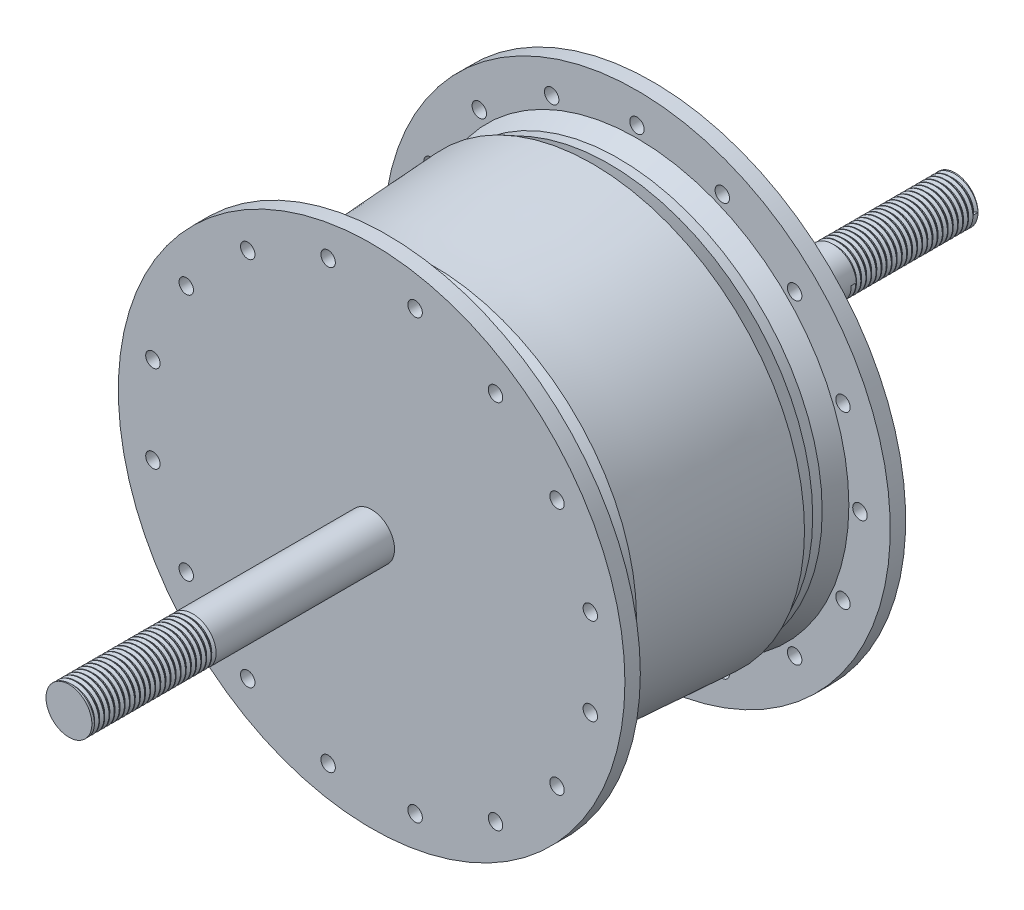
SolidWorks part; units mm, degrees
ref_plane "Front Plane" through (0, 0, 0) normal (0, 0, 1) x (1, 0, 0)
ref_plane "Top Plane" through (0, 0, 0) normal (0, 1, 0) x (1, 0, 0)
ref_plane "Right Plane" through (0, 0, 0) normal (1, 0, 0) x (0, 0, -1)
sketch "Sketch1" plane through (0, 0, 0) normal (1, 0, 0) x (0, 0, -1)
  line L0 (-25.95, 44) -> (-21.711, 41.0448)
  line L1 (-21.711, 41.0448) -> (-20.0488, 41.0448)
  line L2 (-20.0488, 41.0448) -> (-16.448, 42.2998)
  line L3 (-16.448, 42.2998) -> (-8.6389, 42.2998) construction
  line L4 (-8.6389, 42.2998) -> (0, 43.18) construction
  line L5 (0, 43.18) -> (16.7404, 44) construction
  line L6 (16.7404, 44) -> (20.1458, 42.2998)
  line L7 (20.1458, 42.2998) -> (22.1102, 42.2998)
  line L8 (-25.95, 0) -> (-25.95, 44)
  line L9 (25.95, 0) -> (25.95, 44)
  line L10 (-25.95, 0) -> (25.95, 0)
  line L11 (22.1102, 42.2998) -> (25.95, 44)
  spline S0 degree 3 poles (-16.448, 42.2998) (-8.6389, 42.2998) (0, 43.18) (16.7404, 44) knots 0 0 0 0 1 1 1 1
  point P0 (-25.95, 0)
  point P1 (25.95, 0)
  point P2 (-25.95, 44)
  point P3 (25.95, 44)
  point P4 (0, 43.18)
  point P5 (16.7404, 44)
  point P6 (-20.9103, 41.0448)
  point P7 (-8.6389, 42.2998)
  point P8 (-16.448, 42.2998)
  point P9 (21.2028, 42.2998)
  point P10 (23.4339, 44)
  point P11 (-20.9103, 38.6742)
  point P12 (21.2028, 41.0448)
revolve "Revolve1" add sketch "Sketch1" angle 360 about L10
sketch "Sketch2" plane through (0, 0, 25.95) normal (0, 0, 1) x (1, 0, 0)
  circle A0 centre (0, 0) radius 52.6
  circle A17 centre (-9.0327, 45.4104) radius 1.5
  circle A19 centre (9.0327, 45.4104) radius 1.5
  circle A20 centre (25.7229, 38.497) radius 1.5
  circle A21 centre (38.497, 25.7229) radius 1.5
  circle A22 centre (45.4104, 9.0327) radius 1.5
  circle A23 centre (45.4104, -9.0327) radius 1.5
  circle A24 centre (38.497, -25.7229) radius 1.5
  circle A25 centre (25.7229, -38.497) radius 1.5
  circle A26 centre (9.0327, -45.4104) radius 1.5
  circle A27 centre (-9.0327, -45.4104) radius 1.5
  circle A28 centre (-25.7229, -38.497) radius 1.5
  circle A29 centre (-38.497, -25.7229) radius 1.5
  circle A30 centre (-45.4104, -9.0327) radius 1.5
  circle A31 centre (-45.4104, 9.0327) radius 1.5
  circle A32 centre (-38.497, 25.7229) radius 1.5
  circle A33 centre (-25.7229, 38.497) radius 1.5
  dimension "D1" = 16
  dimension "D2" = 46.3
extrude "Boss-Extrude1" add sketch "Sketch2" along normal blind 3.2
sketch "Sketch3" plane through (0, 0, -25.95) normal (0, 0, -1) x (-1, 0, 0)
  circle A0 centre (0, 0) radius 52.6
  circle A1 centre (0, 46.3) radius 1.5
  circle A2 centre (17.7182, 42.7756) radius 1.5
  circle A3 centre (32.739, 32.739) radius 1.5
  circle A4 centre (42.7756, 17.7182) radius 1.5
  circle A5 centre (46.3, 0) radius 1.5
  circle A6 centre (42.7756, -17.7182) radius 1.5
  circle A7 centre (32.739, -32.739) radius 1.5
  circle A8 centre (17.7182, -42.7756) radius 1.5
  circle A9 centre (0, -46.3) radius 1.5
  circle A10 centre (-17.7182, -42.7756) radius 1.5
  circle A11 centre (-32.739, -32.739) radius 1.5
  circle A12 centre (-42.7756, -17.7182) radius 1.5
  circle A13 centre (-46.3, 0) radius 1.5
  circle A14 centre (-42.7756, 17.7182) radius 1.5
  circle A15 centre (-32.739, 32.739) radius 1.5
  circle A16 centre (-17.7182, 42.7756) radius 1.5
  dimension "D1" = 16
extrude "Boss-Extrude2" add sketch "Sketch3" along normal blind 3.2
sketch "Sketch4" plane through (0, 0, 0) normal (0, 0, 1) x (1, 0, 0)
  circle A0 centre (0, 0) radius 4.7625
  point P0 (0, 0)
extrude "Boss-Extrude3" add sketch "Sketch4" along normal blind 92 and the other way blind 92
thread "Thread1" pitch 1.0583 method cut profile "Thread Profile1" start angle 0, offset 0, length 25.4, pitch 1.0583, diameter 9.525
ref_plane "Plane1" through (-4.7625, 0, 92) normal (0, -1, 0) x (-1, 0, 0)
sketch "Thread Profile1" plane through (-4.7625, 0, 92) normal (0, -1, 0) x (-1, 0, 0)
  line L0 (0, 0) -> (0, 1.0583) construction
  line L11 (0, 0) -> (0, 0.926)
  line L12 (0, 0.926) -> (-0.5728, 0.5953)
  line L13 (-0.5728, 0.5953) -> (-0.5728, 0.3307)
  line L15 (-0.5728, 0.3307) -> (0, 0)
  line L17 (-0.5728, 0.463) -> (0, 0.463) construction
  point P2 (0, 0)
  dimension "Pitch" = 1.0583
  dimension "Profile_Angle" = 60
  dimension "Profile_Land" = 0.2646
  dimension "Profile_Height" = 0.5728
thread "Thread2" pitch 1.0583 method cut profile "Thread Profile2" start angle 0, offset 0, length 25.4, pitch 1.0583, diameter 9.525
ref_plane "Plane2" through (4.7625, 0, -92) normal (0, -1, 0) x (1, 0, 0)
sketch "Thread Profile2" plane through (4.7625, 0, -92) normal (0, -1, 0) x (1, 0, 0)
  line L0 (0, 0) -> (0, 1.0583) construction
  line L11 (0, 0) -> (0, 0.926)
  line L12 (0, 0.926) -> (-0.5728, 0.5953)
  line L13 (-0.5728, 0.5953) -> (-0.5728, 0.3307)
  line L15 (-0.5728, 0.3307) -> (0, 0)
  line L17 (-0.5728, 0.463) -> (0, 0.463) construction
  point P2 (0, 0)
  dimension "Pitch" = 1.0583
  dimension "Profile_Angle" = 60
  dimension "Profile_Land" = 0.2646
  dimension "Profile_Height" = 0.5728
